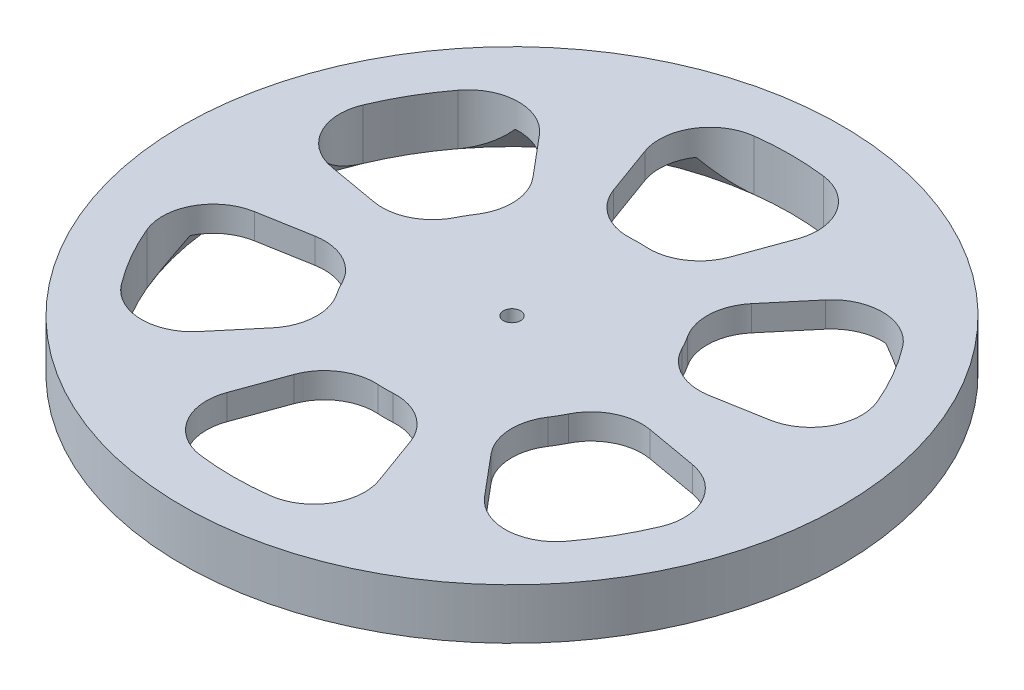
SolidWorks part; units mm, degrees
ref_plane "Front Plane" through (0, 0, 0) normal (0, 0, 1) x (1, 0, 0)
ref_plane "Top Plane" through (0, 0, 0) normal (0, 1, 0) x (1, 0, 0)
ref_plane "Right Plane" through (0, 0, 0) normal (1, 0, 0) x (0, 0, -1)
sketch "Sketch2" plane through (0, 0, 0) normal (0, 0, 1) x (1, 0, 0)
  line L0 (0, 0) -> (-65, 0)
  line L1 (-65, 0) -> (-65, -10)
  line L2 (-65, -10) -> (-55, -10)
  line L3 (-55, -10) -> (-52.1132, -5)
  line L4 (-52.1132, -5) -> (0, -5)
  line L5 (0, 0) -> (0, -5)
  dimension "D1" = 65
  dimension "D2" = 60
  dimension "D3" = 10
  dimension "D4" = 5
  dimension "D5" = 10
revolve "Revolve1" add sketch "Sketch2" angle 360 about L5
sketch "Sketch4" plane through (0, 0, 0) normal (0, 1, 0) x (1, 0, 0)
  line L0 (0, -25) -> (0, -65)
  line L1 (-8.5505, -23.4923) -> (-22.2313, -61.08)
  line L2 (8.5505, -23.4923) -> (22.2313, -61.08)
  circle A0 centre (0, 0) radius 25
  circle A1 centre (0, 0) radius 65 construction
  circle A2 centre (0, 0) radius 65
  circle A3 centre (0, 0) radius 55
  dimension "D1" = 50
  dimension "D4" = 10
  dimension "D2" = 20
  dimension "D3" = 20
extrude "Cut-Extrude1" cut sketch "Sketch4" against normal through all contours L1 A3 L0 A0 | L0 A3 L2 A0 region at (7.2347, 0, 41.0298) region at (-7.2347, 0, 41.0298)
pattern_circular "CirPattern1" count 6 over 360 about axis through (0, 0, 0) along (0, 1, 0) of "Cut-Extrude1" reverse direction yes
fillet "Fillet1" radius 10 24 edges at (-54.1644, -5, 9.5506) (-35.3533, -5, 42.1324) (-16.0697, -2.5, 19.1511) (-24.6202, -2.5, 4.3412) (35.3533, -5, 42.1324) (54.1644, -5, 9.5506) (16.0697, -2.5, 19.1511) (54.1644, -5, -9.5506) (35.3533, -5, -42.1324) (16.0697, -2.5, -19.1511) (24.6202, -2.5, -4.3412) (-35.3533, -5, -42.1324) (-54.1644, -5, -9.5506) (-24.6202, -2.5, -4.3412) (-16.0697, -2.5, -19.1511) (18.8111, -5, -51.6831) (-18.8111, -5, -51.6831) (-8.5505, -2.5, -23.4923) (8.5505, -2.5, -23.4923) (24.6202, -2.5, 4.3412) (-18.8111, -5, 51.6831) (18.8111, -5, 51.6831) (8.5505, -2.5, 23.4923) (-8.5505, -2.5, 23.4923)
sketch "Sketch5" plane through (0, 0, 0) normal (0, 1, 0) x (1, 0, 0)
  circle A0 centre (0, 0) radius 1.7
  dimension "D1" = 3.4
extrude "Cut-Extrude2" cut sketch "Sketch5" against normal through all
